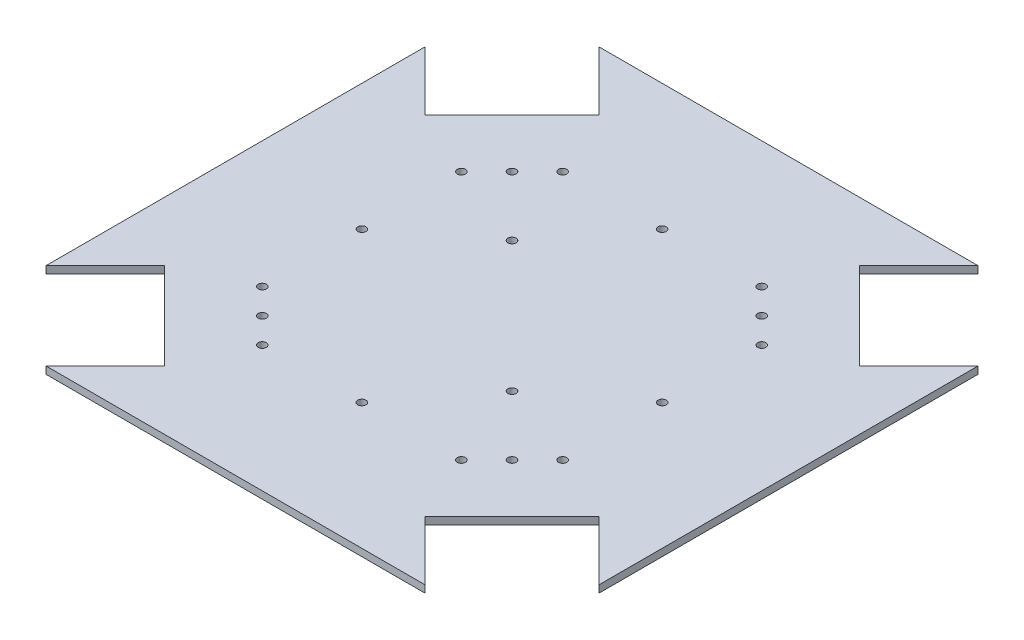
SolidWorks part; units mm, degrees
ref_plane "Front Plane" through (0, 0, 0) normal (0, 0, 1) x (1, 0, 0)
ref_plane "Top Plane" through (0, 0, 0) normal (0, 1, 0) x (1, 0, 0)
ref_plane "Right Plane" through (0, 0, 0) normal (1, 0, 0) x (0, 0, -1)
sketch "Sketch1" plane through (0, 0, 0) normal (0, 1, 0) x (1, 0, 0)
  line L1 (-114.3, 114.3) -> (114.3, 114.3)
  line L2 (-114.3, 114.3) -> (-114.3, -114.3)
  line L3 (-114.3, -114.3) -> (114.3, -114.3)
  line L4 (114.3, 114.3) -> (114.3, -114.3)
  line L5 (-114.3, 114.3) -> (114.3, -114.3) construction
  line L6 (-114.3, -114.3) -> (114.3, 114.3) construction
  point P0 (0, 0)
  point P14 (0, 0)
  dimension "D1" = 228.6
  dimension "D2" = 228.6
extrude "plate" add sketch "Sketch1" along normal blind 3
sketch "Sketch8" plane through (0, 3, 0) normal (0, 1, 0) x (1, 0, 0)
  line L0 (-114.3, 114.3) -> (114.3, -114.3) construction
  line L1 (114.3, 114.3) -> (-114.3, -114.3) construction
  line L2 (-62.6812, 165.9188) -> (165.9188, -62.6812) construction
  line L3 (0, 0) -> (51.6188, 51.6188) construction
  circle A0 centre (51.6188, 51.6188) radius 1.7
  circle A1 centre (62.084, 41.1536) radius 1.7
  circle A2 centre (41.1536, 62.084) radius 1.7
  circle A3 centre (51.6188, -51.6188) radius 1.7
  circle A4 centre (62.084, -41.1536) radius 1.7
  circle A5 centre (41.1536, -62.084) radius 1.7
  circle A6 centre (-51.6188, -51.6188) radius 1.7
  circle A7 centre (-41.1536, -62.084) radius 1.7
  circle A8 centre (-62.084, -41.1536) radius 1.7
  circle A9 centre (-51.6188, 51.6188) radius 1.7
  circle A10 centre (-62.084, 41.1536) radius 1.7
  circle A11 centre (-41.1536, 62.084) radius 1.7
  dimension "D2" = 3.4
  dimension "D3" = 3.4
  dimension "D4" = 3.4
  dimension "D5" = 14.8
  dimension "D6" = 14.8
  dimension "D8" = 73
  dimension "D9" = 73
  dimension "D1" = 73
  dimension "D7" = 4
extrude "motor-mount-holes" cut sketch "Sketch8" against normal blind 3
sketch "Sketch9" plane through (0, 3, 0) normal (0, 1, 0) x (1, 0, 0)
  line L0 (-114.3, -114.3) -> (114.3, 114.3) construction
  line L1 (114.3, 114.3) -> (-114.3, 114.3) construction
  line L2 (114.3, -114.3) -> (114.3, 114.3) construction
  line L3 (-114.3, 114.3) -> (114.3, -114.3) construction
  circle A0 centre (-26.962, 26.962) radius 1.7
  circle A1 centre (26.962, -26.962) radius 1.7
  dimension "D3" = 3.4
  dimension "D4" = 3.4
  dimension "D1" = 76.26
  dimension "D2" = 38.13
extrude "connector-board-holes" cut sketch "Sketch9" against normal blind 3
sketch "Sketch10" plane through (0, 3, 0) normal (0, 1, 0) x (1, 0, 0)
  line L0 (0, 114.3) -> (0, -114.3) construction
  line L1 (114.3, 114.3) -> (-114.3, 114.3) construction
  line L2 (-114.3, -114.3) -> (114.3, -114.3) construction
  line L3 (-114.3, 0) -> (114.3, 0) construction
  line L4 (-114.3, 114.3) -> (-114.3, -114.3) construction
  line L5 (114.3, -114.3) -> (114.3, 114.3) construction
  line L6 (0, 0) -> (0, 62.08) construction
  circle A1 centre (0, 62.08) radius 1.7
  circle A2 centre (62.08, 0) radius 1.7
  circle A3 centre (0, -62.08) radius 1.7
  circle A4 centre (-62.08, 0) radius 1.7
  dimension "D1" = 3.4
  dimension "D2" = 62.08
  dimension "D4" = 62.08
  dimension "D5" = 62.08
  dimension "D3" = 4
extrude "level2-standoff-holes" cut sketch "Sketch10" against normal blind 3
sketch "Sketch2" plane through (0, 3, 0) normal (0, 1, 0) x (1, 0, 0)
  line L0 (-114.3, -114.3) -> (114.3, 114.3) construction
  line L1 (114.3, -114.3) -> (-114.3, 114.3) construction
  line L2 (-96.3395, -132.2605) -> (132.2605, 96.3395) construction
  line L3 (-132.2605, -96.3395) -> (96.3395, 132.2605) construction
  line L4 (186.142, -42.458) -> (-42.458, 186.142) construction
  line L5 (114.3, 114.3) -> (78.379, 114.3)
  line L6 (114.3, 114.3) -> (-114.3, 114.3) construction
  line L7 (78.379, 114.3) -> (53.8815, 89.8026)
  line L8 (53.8815, 89.8026) -> (89.8026, 53.8815)
  line L9 (89.8026, 53.8815) -> (114.3, 78.379)
  line L10 (114.3, 78.379) -> (114.3, 114.3)
  line L11 (78.379, -114.3) -> (114.3, -114.3)
  line L12 (114.3, -114.3) -> (114.3, -78.379)
  line L13 (114.3, -78.379) -> (89.8026, -53.8815)
  line L14 (89.8026, -53.8815) -> (53.8815, -89.8026)
  line L15 (53.8815, -89.8026) -> (78.379, -114.3)
  line L16 (-114.3, -78.379) -> (-114.3, -114.3)
  line L17 (-114.3, -114.3) -> (-78.379, -114.3)
  line L18 (-78.379, -114.3) -> (-53.8815, -89.8026)
  line L19 (-53.8815, -89.8026) -> (-89.8026, -53.8815)
  line L20 (-89.8026, -53.8815) -> (-114.3, -78.379)
  line L21 (-78.379, 114.3) -> (-114.3, 114.3)
  line L22 (-114.3, 114.3) -> (-114.3, 78.379)
  line L23 (-114.3, 78.379) -> (-89.8026, 53.8815)
  line L24 (-89.8026, 53.8815) -> (-53.8815, 89.8026)
  line L25 (-53.8815, 89.8026) -> (-78.379, 114.3)
  line L26 (0, 0) -> (89.8026, 53.8815) construction
  line L27 (0, 0) -> (53.8815, -89.8026) construction
  dimension "D5" = 90
  dimension "D6" = 14.036
  dimension "D7" = 104.7269
  dimension "D1" = 25.4
  dimension "D2" = 25.4
  dimension "D3" = 101.6
  dimension "D4" = 4
extrude "wheel-slots" cut sketch "Sketch2" against normal blind 3
